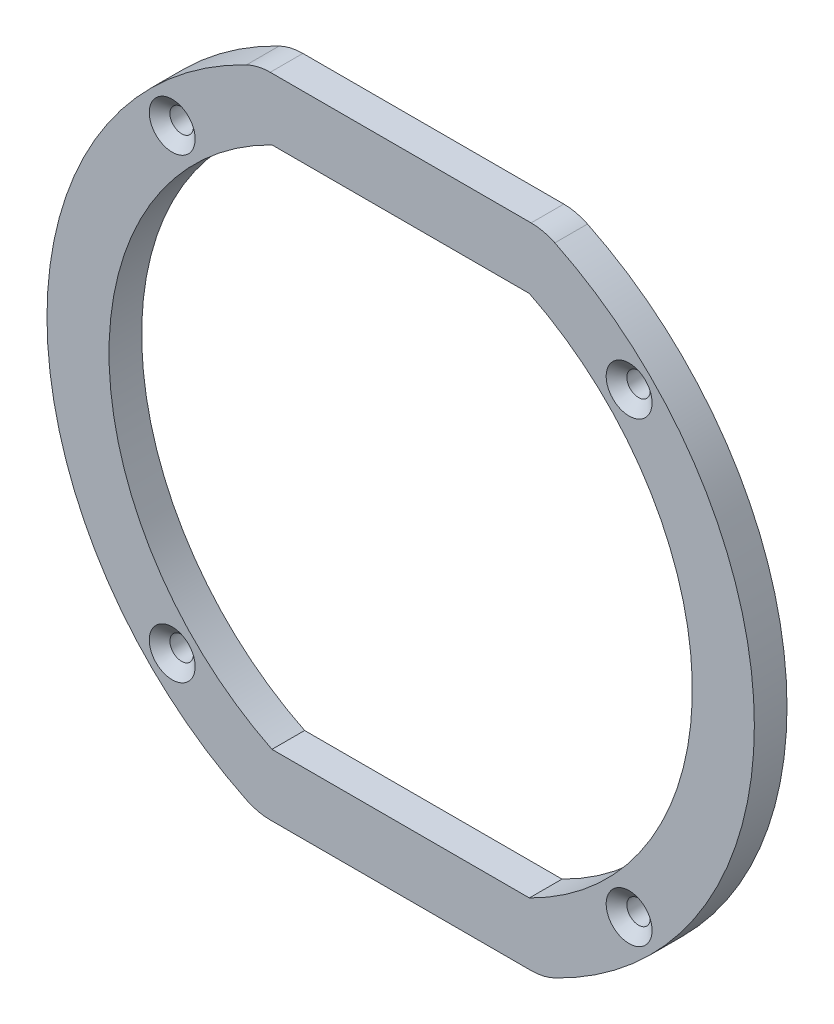
SolidWorks part; units mm, degrees
material "PVC 0.007 Plasticized"
ref_plane "Front Plane" through (0, 0, 0) normal (0, 0, 1) x (1, 0, 0)
ref_plane "Top Plane" through (0, 0, 0) normal (0, 1, 0) x (1, 0, 0)
ref_plane "Right Plane" through (0, 0, 0) normal (1, 0, 0) x (0, 0, -1)
sketch "Sketch1" plane through (0, 0, 0) normal (0, 0, 1) x (1, 0, 0)
  line L0 (0, -48.1) -> (0, 48.1) construction
  line L1 (-23.6506, 48.1) -> (23.6506, 48.1)
  line L2 (-23.6506, -48.1) -> (23.6506, -48.1)
  line L3 (0, -59.5) -> (0, 59.5) construction
  line L4 (-26.1677, 59.5) -> (26.1677, 59.5)
  line L5 (-26.1677, -59.5) -> (26.1677, -59.5)
  arc A0 (-26.1677, 59.5) -> (-26.1677, -59.5) centre (0, 0) ccw
  arc A1 (-23.6506, 48.1) -> (-23.6506, -48.1) centre (0, 0) ccw
  arc A2 (23.6506, -48.1) -> (23.6506, 48.1) centre (0, 0) ccw
  arc A3 (26.1677, -59.5) -> (26.1677, 59.5) centre (0, 0) ccw
  point P6 (0, 0)
  point P9 (0, 48.1)
  point P13 (0, -48.1)
  point P15 (0, 0)
  point P17 (0, 59.5)
  point P20 (0, -59.5)
  dimension "D1" = 130
  dimension "D2" = 107.2
  dimension "D3" = 96.2
  dimension "D4" = 119
extrude "Boss-Extrude1" add sketch "Sketch1" along normal blind 6
hole_wizard "CSK for #8 Flat Head Machine Screw (100)1" positions "Sketch2" profile "Sketch4" countersink size "#8" standard "ANSI Inch" end condition through all
sketch "Sketch2" plane through (0, 0, 6) normal (0, 0, 1) x (1, 0, 0)
  line L1 (-41.985, -41.985) -> (41.985, -41.985) construction
  line L2 (-41.985, -41.985) -> (-41.985, 41.985) construction
  line L3 (-41.985, 41.985) -> (41.985, 41.985) construction
  line L4 (41.985, -41.985) -> (41.985, 41.985) construction
  line L5 (-41.985, -41.985) -> (41.985, 41.985) construction
  line L6 (-41.985, 41.985) -> (41.985, -41.985) construction
  point P1 (0, 0)
  point P2 (41.985, 41.985)
  point P39 (-41.985, -41.985)
  point P40 (-41.985, 41.985)
  point P41 (41.985, -41.985)
  dimension "D1" = 83.97
sketch "Sketch4" plane through (0, 0, 6) normal (1, 0, 0) x (0, -1, 0)
  line L0 (0, 0) -> (0, 6)
  line L1 (0, 6) -> (2.1526, 6)
  line L2 (2.1526, 6) -> (2.1526, 1.7317)
  line L3 (2.1526, 1.7317) -> (4.2164, 0)
  line L5 (4.2164, 0) -> (0, 0)
  line L6 (-2.1526, 1.7317) -> (-4.2164, 0) construction
  line L11 (0, -6.35) -> (0, 107.95) construction
  dimension "Thru Hole Dia." = 4.3053
  dimension "Thru Hole Depth" = 6
  dimension "Near C'Sink Dia." = 8.4328
  dimension "Near C'Sink Angle" = 100
sketch "Sketch5" plane through (0, 0, 0) normal (0, 0, -1) x (-1, 0, 0)
  line L0 (59.2455, 0) -> (-59.2455, 0) construction
  circle A0 centre (-59.2455, 0) radius 1.905
  circle A1 centre (59.2455, 0) radius 1.905
  point P4 (0, 0)
  dimension "D2" = 3.81
  dimension "D1" = 118.491
extrude "Boss-Extrude2" add sketch "Sketch5" along normal blind 2.5
fillet "Fillet1" radius 10 4 edges at (26.1677, -59.5, 3) (-26.1677, -59.5, 3) (26.1677, 59.5, 3) (-26.1677, 59.5, 3)
